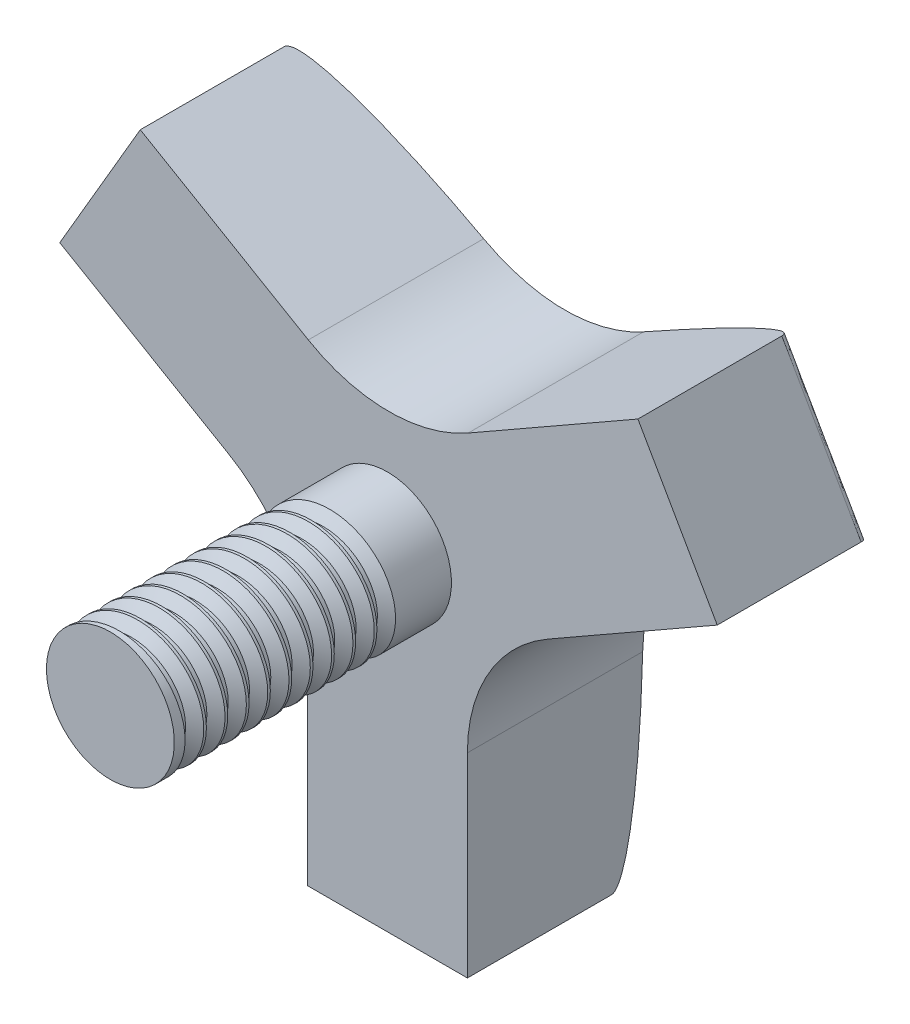
SolidWorks part; units mm, degrees
ref_plane "Alzado" through (0, 0, 0) normal (0, 0, 1) x (1, 0, 0)
ref_plane "Planta" through (0, 0, 0) normal (0, 1, 0) x (1, 0, 0)
ref_plane "Vista lateral" through (0, 0, 0) normal (1, 0, 0) x (0, 0, -1)
sketch "Croquis2" plane through (0, 0, 0) normal (0, 0, 1) x (1, 0, 0)
  line L0 (5.0382, 8.6381) -> (15.6536, 14.7045)
  line L1 (0.0255, 5.7734) -> (-5.0127, -2.8646)
  line L2 (-5.0127, -2.8646) -> (4.9872, -2.9088)
  line L3 (4.9872, -2.9088) -> (0.0255, 5.7734)
  line L4 (15.6536, 14.7045) -> (20.6153, 6.0222)
  line L5 (20.6153, 6.0222) -> (10.0255, -0.0296)
  line L6 (4.9872, -8.7118) -> (4.9872, -20.9088)
  line L7 (4.9872, -20.9088) -> (-5.0127, -20.9088)
  line L8 (-5.0127, -20.9088) -> (-5.0127, -8.6087)
  line L9 (-9.9745, 0.0294) -> (-20.5103, 6.1745)
  line L10 (-20.5103, 6.1745) -> (-15.4721, 14.8126)
  line L11 (-15.4721, 14.8126) -> (-4.9617, 8.6823)
  circle A0 centre (0, 0) radius 2.8868 construction
  arc A1 (-9.9745, 0.0294) -> (-5.0127, -8.6087) centre (-15.0127, -8.6087) cw
  arc A2 (4.9872, -8.7118) -> (10.0255, -0.0296) centre (14.9872, -8.7118) cw
  arc A3 (5.0382, 8.6381) -> (-4.9617, 8.6823) centre (0.0766, 17.3203) cw
  dimension "D5" = 10
  dimension "D1" = 90
  dimension "D2" = 90
  dimension "D3" = 10
  dimension "D4" = 18
extrude "Saliente-Extruir1" add sketch "Croquis2" along normal blind 11 contours A3 L0 L4 L5 A2 L6 L7 L8 A1 L9 L10 L11
ref_axis "Eje1" through (0, 0, -58.0678) along (0, 0, 1)
fillet "Redondeo1" radius 2 3 edges at (-17.9912, 10.4935, 0) (18.1344, 10.3633, 0) (-0.0128, -20.9088, 0) second distance 15 first distance on face at (-17.9912, 10.4935, 5.5) first distance on face at (18.1344, 10.3633, 5.5) first distance on face at (-0.0128, -20.9088, 5.5)
scale "Escala1" bodies to scale 106 105 scale about centroid uniform scaling yes scale factor 0.75
sketch "Croquis7" plane through (0, 0, 9.6631) normal (0, 0, 1) x (1, 0, 0)
  circle A0 centre (0, 0) radius 3
  dimension "D1" = 6
extrude "Saliente-Extruir2" add sketch "Croquis7" along normal blind 13
thread "Rosca1" pitch 1 method cut profile "Perfil de rosca1" start angle 0, offset 0, length 10, pitch 1, diameter 6
ref_plane "Plano1" through (-3, 0, 22.6631) normal (0, -1, 0) x (-1, 0, 0)
sketch "Perfil de rosca1" plane through (-3, 0, 22.6631) normal (0, -1, 0) x (-1, 0, 0)
  line L0 (0, 0) -> (0, 1) construction
  line L11 (0, 0) -> (0, 0.875)
  line L12 (0, 0.875) -> (-0.5413, 0.5625)
  line L13 (-0.5413, 0.5625) -> (-0.5413, 0.3125)
  line L15 (-0.5413, 0.3125) -> (0, 0)
  line L17 (-0.5413, 0.4375) -> (0, 0.4375) construction
  point P2 (0, 0)
  dimension "Pitch" = 1
  dimension "Profile_Angle" = 60
  dimension "Profile_Land" = 0.25
  dimension "Profile_Height" = 0.5413
split "Partir2" bodies to split 110 resulting bodies 111 112 split by face at (-3, 0, 9.6631)
